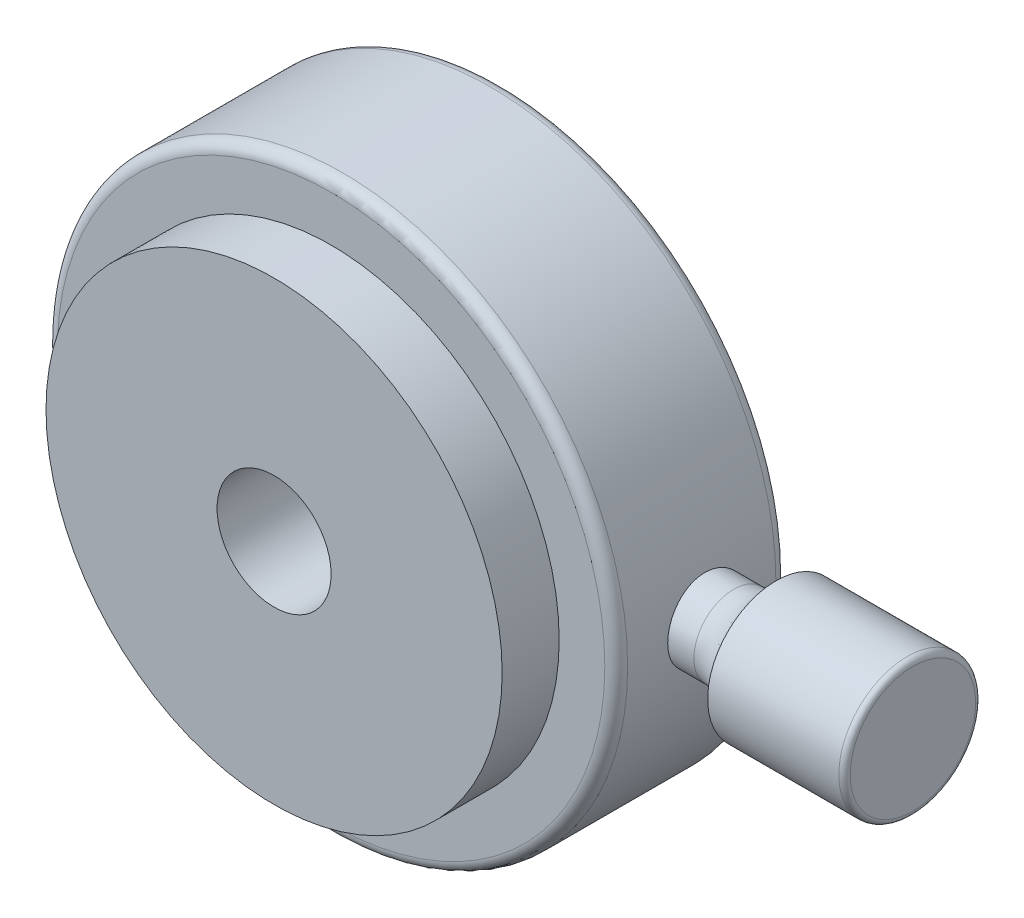
SolidWorks part; units mm, degrees
ref_plane "前视基准面" through (0, 0, 0) normal (0, 0, 1) x (1, 0, 0)
ref_plane "上视基准面" through (0, 0, 0) normal (0, 1, 0) x (1, 0, 0)
ref_plane "右视基准面" through (0, 0, 0) normal (1, 0, 0) x (0, 0, -1)
sketch "草图1" plane through (0, 0, 0) normal (0, 0, 1) x (1, 0, 0)
  circle A0 centre (0, 0) radius 25
extrude "凸台-拉伸1" add sketch "草图1" along normal blind 20
sketch "草图2" plane through (0, 0, 20) normal (0, 0, 1) x (1, 0, 0)
  circle A0 centre (0, 0) radius 5
extrude "切除-拉伸1" cut sketch "草图2" against normal blind 10
sketch "草图3" plane through (0, 0, 10) normal (0, 0, 1) x (1, 0, 0)
  circle A0 centre (0, 0) radius 10
extrude "切除-拉伸2" cut sketch "草图3" against normal blind 5
sketch "草图4" plane through (0, 0, 20) normal (0, 0, 1) x (1, 0, 0)
  circle A0 centre (0, 0) radius 25
extrude "切除-拉伸3" cut sketch "草图4" against normal blind 5
sketch "草图5" plane through (0, 0, 15) normal (0, 0, 1) x (1, 0, 0)
  circle A0 centre (0, 0) radius 5
  circle A1 centre (0, 0) radius 20
extrude "凸台-拉伸2" add sketch "草图5" along normal blind 5
ref_plane "基准面4" through (24, 0, 0) normal (1, 0, 0) x (0, 0, -1)
sketch "草图6" plane through (24, 0, 0) normal (1, 0, 0) x (0, 0, -1)
  circle A0 centre (-6.9832, 0) radius 3.5
extrude "凸台-拉伸3" add sketch "草图6" along normal blind 7
sketch "草图7" plane through (31, 0, 0) normal (1, 0, 0) x (0, 0, -1)
  circle A0 centre (-6.9832, 0) radius 6
extrude "凸台-拉伸4" add sketch "草图7" along normal blind 12
fillet "圆角1" radius 4 1 edges at (31, 0, 3.4832)
fillet "圆角2" radius 0.5 1 edges at (43, 0, 0.9832)
fillet "圆角3" radius 1 1 edges at (25, 0, 0)
fillet "圆角4" radius 1 1 edges at (25, 0, 15)
